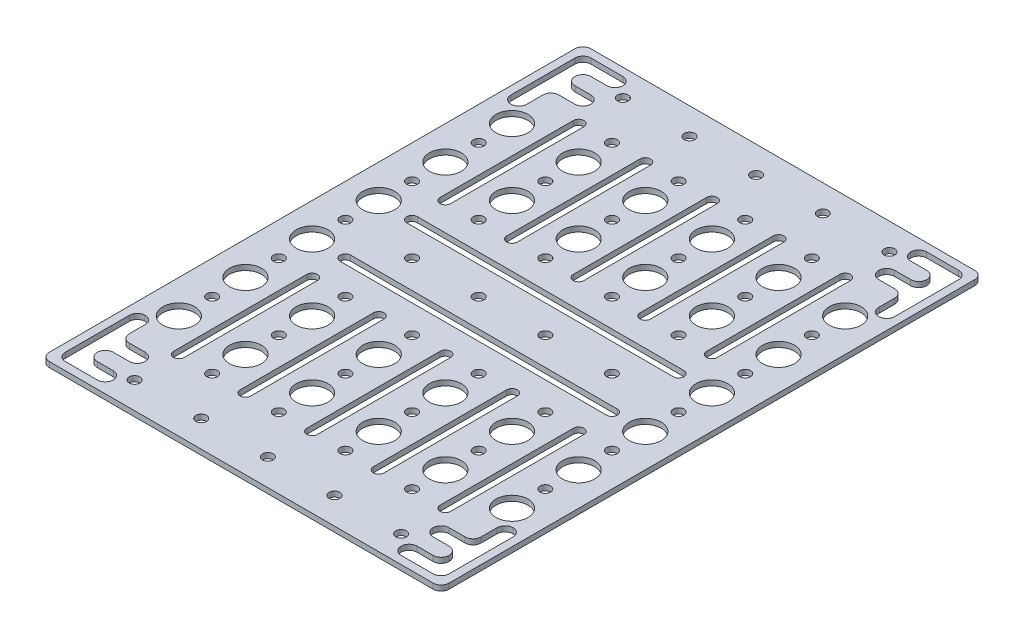
SolidWorks part; units mm, degrees
ref_plane "前视基准面" through (0, 0, 0) normal (0, 0, 1) x (1, 0, 0)
ref_plane "上视基准面" through (0, 0, 0) normal (0, 1, 0) x (1, 0, 0)
ref_plane "右视基准面" through (0, 0, 0) normal (1, 0, 0) x (0, 0, -1)
sketch "草图1" plane through (0, 0, 0) normal (0, 1, 0) x (1, 0, 0)
  line L1 (-75, 101.6) -> (75, 101.6)
  line L2 (-75, 101.6) -> (-75, -101.6)
  line L3 (-75, -101.6) -> (75, -101.6)
  line L4 (75, 101.6) -> (75, -101.6)
  line L5 (-75, 101.6) -> (75, -101.6) construction
  line L6 (-75, -101.6) -> (75, 101.6) construction
  point P0 (0, 0)
  dimension "D1" = 150
  dimension "D2" = 203.2
extrude "凸台-拉伸1" add sketch "草图1" along normal blind 2
sketch "草图2" plane through (0, 2, 0) normal (0, 1, 0) x (1, 0, 0)
  line L0 (75, -91.6) -> (-75, -91.6) construction
  line L1 (75, -101.6) -> (75, 101.6) construction
  line L2 (-75, 101.6) -> (-75, -101.6) construction
  line L3 (-75, -101.6) -> (75, -101.6) construction
  line L4 (-75, 91.6) -> (75, 91.6) construction
  line L5 (75, 101.6) -> (-75, 101.6) construction
  line L6 (-1.1, 0) -> (1.1, 0) construction
  line L7 (-75, 0) -> (75, 0) construction
  line L8 (0, 101.6) -> (0, -101.6) construction
  line L9 (-50, 75) -> (-50, 25) construction
  line L10 (-48, 75) -> (-48, 25)
  line L11 (-52, 75) -> (-52, 25)
  line L12 (-25, 75) -> (-25, 25) construction
  line L13 (-23, 75) -> (-23, 25)
  line L14 (-27, 75) -> (-27, 25)
  line L15 (0, 75) -> (0, 25) construction
  line L16 (2, 75) -> (2, 25)
  line L17 (-2, 75) -> (-2, 25)
  line L18 (25, 75) -> (25, 25) construction
  line L19 (27, 75) -> (27, 25)
  line L20 (23, 75) -> (23, 25)
  line L21 (50, 75) -> (50, 25) construction
  line L22 (52, 75) -> (52, 25)
  line L23 (48, 75) -> (48, 25)
  line L24 (-50, -75) -> (-50, -25) construction
  line L25 (-48, -75) -> (-48, -25)
  line L26 (-52, -75) -> (-52, -25)
  line L27 (-25, -75) -> (-25, -25) construction
  line L28 (-23, -75) -> (-23, -25)
  line L29 (-27, -75) -> (-27, -25)
  line L30 (0, -75) -> (0, -25) construction
  line L31 (2, -75) -> (2, -25)
  line L32 (-2, -75) -> (-2, -25)
  line L33 (25, -75) -> (25, -25) construction
  line L34 (27, -75) -> (27, -25)
  line L35 (23, -75) -> (23, -25)
  line L36 (50, -75) -> (50, -25) construction
  line L37 (52, -75) -> (52, -25)
  line L38 (48, -75) -> (48, -25)
  line L39 (-50, 12.5) -> (50, 12.5) construction
  line L40 (-50, 14.5) -> (50, 14.5)
  line L41 (-50, 10.5) -> (50, 10.5)
  line L42 (-50, -12.5) -> (50, -12.5) construction
  line L43 (-50, -14.5) -> (50, -14.5)
  line L44 (-50, -10.5) -> (50, -10.5)
  line L57 (-75, 75) -> (-50, 75) construction
  line L58 (-62.5, 75) -> (-62.5, 50) construction
  circle A0 centre (-50, 91.6) radius 2
  circle A4 centre (-25, 91.6) radius 2
  circle A5 centre (0, 91.6) radius 2
  circle A6 centre (25, 91.6) radius 2
  circle A7 centre (50, 91.6) radius 2
  circle A8 centre (50, -91.6) radius 2
  circle A9 centre (25, -91.6) radius 2
  circle A10 centre (0, -91.6) radius 2
  circle A11 centre (-25, -91.6) radius 2
  circle A12 centre (-50, -91.6) radius 2
  arc A13 (-48, 75) -> (-52, 75) centre (-50, 75) ccw
  arc A14 (-52, 25) -> (-48, 25) centre (-50, 25) ccw
  arc A15 (-23, 75) -> (-27, 75) centre (-25, 75) ccw
  arc A16 (-27, 25) -> (-23, 25) centre (-25, 25) ccw
  arc A17 (2, 75) -> (-2, 75) centre (0, 75) ccw
  arc A18 (-2, 25) -> (2, 25) centre (0, 25) ccw
  arc A19 (27, 75) -> (23, 75) centre (25, 75) ccw
  arc A20 (23, 25) -> (27, 25) centre (25, 25) ccw
  arc A21 (52, 75) -> (48, 75) centre (50, 75) ccw
  arc A22 (48, 25) -> (52, 25) centre (50, 25) ccw
  arc A23 (-48, -75) -> (-52, -75) centre (-50, -75) cw
  arc A24 (-52, -25) -> (-48, -25) centre (-50, -25) cw
  arc A25 (-23, -75) -> (-27, -75) centre (-25, -75) cw
  arc A26 (-27, -25) -> (-23, -25) centre (-25, -25) cw
  arc A27 (2, -75) -> (-2, -75) centre (0, -75) cw
  arc A28 (-2, -25) -> (2, -25) centre (0, -25) cw
  arc A29 (27, -75) -> (23, -75) centre (25, -75) cw
  arc A30 (23, -25) -> (27, -25) centre (25, -25) cw
  arc A31 (52, -75) -> (48, -75) centre (50, -75) cw
  arc A32 (48, -25) -> (52, -25) centre (50, -25) cw
  arc A33 (-50, 14.5) -> (-50, 10.5) centre (-50, 12.5) ccw
  arc A34 (50, 10.5) -> (50, 14.5) centre (50, 12.5) ccw
  arc A35 (-50, -14.5) -> (-50, -10.5) centre (-50, -12.5) cw
  arc A36 (50, -10.5) -> (50, -14.5) centre (50, -12.5) cw
  circle A38 centre (-62.5, 0) radius 2
  circle A39 centre (-37.5, 0) radius 2
  circle A40 centre (-12.5, 0) radius 2
  circle A41 centre (12.5, 0) radius 2
  circle A42 centre (37.5, 0) radius 2
  circle A43 centre (62.5, 0) radius 2
  circle A44 centre (-37.5, 25) radius 2
  circle A45 centre (-12.5, 25) radius 2
  circle A46 centre (12.5, 25) radius 2
  circle A47 centre (37.5, 25) radius 2
  circle A48 centre (62.5, 25) radius 2
  circle A49 centre (-37.5, 50) radius 2
  circle A50 centre (-12.5, 50) radius 2
  circle A51 centre (12.5, 50) radius 2
  circle A52 centre (37.5, 50) radius 2
  circle A53 centre (62.5, 50) radius 2
  circle A54 centre (-37.5, 75) radius 2
  circle A55 centre (-12.5, 75) radius 2
  circle A56 centre (12.5, 75) radius 2
  circle A57 centre (37.5, 75) radius 2
  circle A59 centre (-62.5, 25) radius 2
  circle A60 centre (-62.5, 50) radius 2
  circle A62 centre (62.5, -25) radius 2
  circle A63 centre (37.5, -25) radius 2
  circle A64 centre (12.5, -25) radius 2
  circle A65 centre (-12.5, -25) radius 2
  circle A66 centre (-37.5, -25) radius 2
  circle A67 centre (-62.5, -25) radius 2
  circle A68 centre (-62.5, -50) radius 2
  circle A69 centre (-37.5, -50) radius 2
  circle A70 centre (-12.5, -50) radius 2
  circle A71 centre (12.5, -50) radius 2
  circle A72 centre (37.5, -50) radius 2
  circle A73 centre (62.5, -50) radius 2
  circle A75 centre (37.5, -75) radius 2
  circle A76 centre (12.5, -75) radius 2
  circle A77 centre (-12.5, -75) radius 2
  circle A78 centre (-37.5, -75) radius 2
  circle A80 centre (-62.5, 62.5) radius 6
  circle A81 centre (-37.5, 62.5) radius 6
  circle A82 centre (-12.5, 62.5) radius 6
  circle A83 centre (12.5, 62.5) radius 6
  circle A84 centre (37.5, 62.5) radius 6
  circle A85 centre (62.5, 62.5) radius 6
  circle A86 centre (-37.5, 37.5) radius 6
  circle A87 centre (-12.5, 37.5) radius 6
  circle A88 centre (12.5, 37.5) radius 6
  circle A89 centre (37.5, 37.5) radius 6
  circle A90 centre (62.5, 37.5) radius 6
  circle A95 centre (62.5, 12.5) radius 6
  circle A100 centre (62.5, -12.5) radius 6
  circle A101 centre (-37.5, -37.5) radius 6
  circle A102 centre (-12.5, -37.5) radius 6
  circle A103 centre (12.5, -37.5) radius 6
  circle A104 centre (37.5, -37.5) radius 6
  circle A105 centre (62.5, -37.5) radius 6
  circle A106 centre (-37.5, -62.5) radius 6
  circle A107 centre (-12.5, -62.5) radius 6
  circle A108 centre (12.5, -62.5) radius 6
  circle A109 centre (37.5, -62.5) radius 6
  circle A110 centre (62.5, -62.5) radius 6
  circle A111 centre (-62.5, 37.5) radius 6
  circle A112 centre (-62.5, 12.5) radius 6
  circle A113 centre (-62.5, -12.5) radius 6
  circle A114 centre (-62.5, -37.5) radius 6
  circle A115 centre (-62.5, -62.5) radius 6
  circle A116 centre (-37.5, 12.5) radius 6 [skipped]
  circle A117 centre (-12.5, 12.5) radius 6 [skipped]
  circle A118 centre (12.5, 12.5) radius 6 [skipped]
  circle A119 centre (37.5, 12.5) radius 6 [skipped]
  circle A120 centre (37.5, -12.5) radius 6 [skipped]
  circle A121 centre (12.5, -12.5) radius 6 [skipped]
  circle A122 centre (-12.5, -12.5) radius 6 [skipped]
  circle A123 centre (-37.5, -12.5) radius 6 [skipped]
  circle A124 centre (-62.5, 75) radius 2 [skipped]
  circle A125 centre (62.5, 75) radius 2 [skipped]
  point P40 (-50, 50)
  point P48 (-25, 50)
  point P55 (0, 50)
  point P62 (25, 50)
  point P69 (50, 50)
  point P75 (-50, -50)
  point P82 (-25, -50)
  point P89 (0, -50)
  point P96 (25, -50)
  point P103 (50, -50)
  point P110 (0, 12.5)
  point P119 (0, -12.5)
  dimension "D3" = 4
  dimension "D7" = 50
  dimension "D8" = 2
  dimension "D13" = 2
  dimension "D16" = 4
  dimension "D23" = 12
  dimension "D24" = 6
  dimension "D30" = 39.1
  dimension "D1" = 10
  dimension "D2" = 10
  dimension "D4" = 25
  dimension "D6" = 25
  dimension "D9" = 50
  dimension "D10" = 25
  dimension "D12" = 25
  dimension "D14" = 12.5
  dimension "D15" = 50
  dimension "D17" = 12.5
  dimension "D20" = 25
  dimension "D21" = 25
  dimension "D22" = 12.5
  dimension "D25" = 6
  dimension "D26" = 25
  dimension "D27" = 25
  dimension "D28" = 12.5
  dimension "D29" = 12.5
  dimension "D5" = 5
  dimension "D11" = 5
  dimension "D18" = 6
  dimension "D19" = 4
extrude "切除-拉伸1" cut sketch "草图2" against normal through all
sketch "草图3" plane through (0, 2, 0) normal (0, 1, 0) x (1, 0, 0)
  line L0 (-72, 98.6) -> (-54, 98.6)
  line L1 (-54, 98.6) -> (-54, 92.6)
  line L2 (-54, 92.6) -> (-66, 92.6)
  line L3 (-66, 92.6) -> (-66, 86.6)
  line L4 (-66, 86.6) -> (-54, 86.6)
  line L5 (-54, 86.6) -> (-54, 80.6)
  line L6 (-54, 80.6) -> (-66, 80.6)
  line L7 (-66, 80.6) -> (-66, 68.6)
  line L8 (-66, 68.6) -> (-72, 68.6)
  line L9 (-72, 68.6) -> (-72, 98.6)
  line L10 (75, 101.6) -> (-75, 101.6) construction
  line L11 (-75, 101.6) -> (-75, -101.6) construction
  line L12 (0, -1.1) -> (0, 1.1) construction
  line L13 (66, 68.6) -> (72, 68.6)
  line L14 (66, 80.6) -> (66, 68.6)
  line L15 (54, 80.6) -> (66, 80.6)
  line L16 (54, 86.6) -> (54, 80.6)
  line L17 (66, 86.6) -> (54, 86.6)
  line L18 (66, 92.6) -> (66, 86.6)
  line L19 (54, 92.6) -> (66, 92.6)
  line L20 (54, 98.6) -> (54, 92.6)
  line L21 (72, 98.6) -> (54, 98.6)
  line L22 (72, 68.6) -> (72, 98.6)
  line L23 (-1.1, 0) -> (1.1, 0) construction
  line L24 (-66, -68.6) -> (-72, -68.6)
  line L25 (-66, -80.6) -> (-66, -68.6)
  line L26 (-54, -80.6) -> (-66, -80.6)
  line L27 (-54, -86.6) -> (-54, -80.6)
  line L28 (-66, -86.6) -> (-54, -86.6)
  line L29 (-66, -92.6) -> (-66, -86.6)
  line L30 (-54, -92.6) -> (-66, -92.6)
  line L31 (-54, -98.6) -> (-54, -92.6)
  line L32 (-72, -98.6) -> (-54, -98.6)
  line L33 (-72, -68.6) -> (-72, -98.6)
  line L34 (66, -80.6) -> (66, -68.6)
  line L35 (54, -80.6) -> (66, -80.6)
  line L36 (54, -86.6) -> (54, -80.6)
  line L37 (66, -86.6) -> (54, -86.6)
  line L38 (66, -92.6) -> (66, -86.6)
  line L39 (54, -92.6) -> (66, -92.6)
  line L40 (54, -98.6) -> (54, -92.6)
  line L41 (72, -98.6) -> (54, -98.6)
  line L42 (72, -68.6) -> (72, -98.6)
  line L43 (66, -68.6) -> (72, -68.6)
  dimension "D1" = 6
  dimension "D2" = 6
  dimension "D3" = 12
  dimension "D4" = 12
  dimension "D5" = 3
  dimension "D6" = 3
extrude "切除-拉伸2" cut sketch "草图3" against normal through all
fillet "圆角1" radius 3 44 edges at (72, 1, 68.6) (72, 1, 98.6) (54, 1, 98.6) (54, 1, 86.6) (66, 1, 86.6) (54, 1, 80.6) (66, 1, 80.6) (66, 1, 68.6) (54, 1, 92.6) (66, 1, 92.6) (75, 1, 101.6) (-72, 1, 68.6) (-66, 1, 68.6) (-54, 1, 80.6) (-75, 1, 101.6) (-72, 1, 98.6) (-66, 1, 80.6) (-54, 1, 86.6) (-66, 1, 86.6) (-66, 1, 92.6) (-54, 1, 98.6) (72, 1, -68.6) (66, 1, -68.6) (72, 1, -98.6) (54, 1, -86.6) (54, 1, -98.6) (66, 1, -80.6) (54, 1, -80.6) (66, 1, -86.6) (66, 1, -92.6) (54, 1, -92.6) (75, 1, -101.6) (-72, 1, -68.6) (-66, 1, -68.6) (-54, 1, -80.6) (-66, 1, -80.6) (-75, 1, -101.6) (-54, 1, -98.6) (-54, 1, -86.6) (-66, 1, -86.6) (-66, 1, -92.6) (-72, 1, -98.6) (-54, 1, -92.6) (-54, 1, 92.6)
